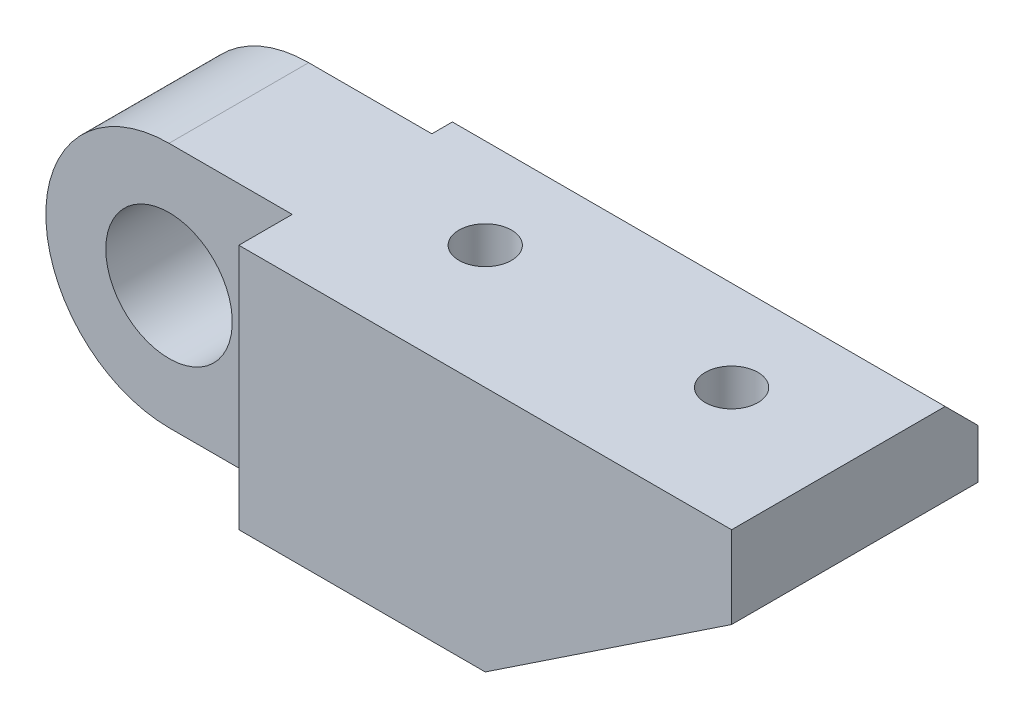
SolidWorks part; units mm, degrees
ref_plane "Front Plane" through (0, 0, 0) normal (0, 0, 1) x (1, 0, 0)
ref_plane "Top Plane" through (0, 0, 0) normal (0, 1, 0) x (1, 0, 0)
ref_plane "Right Plane" through (0, 0, 0) normal (1, 0, 0) x (0, 0, -1)
sketch "Sketch1" plane through (0, 0, 0) normal (0, 0, 1) x (1, 0, 0)
  line L0 (0, 0) -> (-15, 0)
  line L1 (0, 0) -> (60, 0)
  line L2 (0, 0) -> (0, -30)
  line L3 (0, -30) -> (60, -30)
  line L4 (60, 0) -> (60, -30)
  line L5 (-30, -15) -> (-30, 3.2539)
  line L6 (0, -30) -> (-15, -30)
  line L7 (0, 0) -> (0, -30)
  line L8 (-15, -30) -> (0, -30)
  line L9 (-15, 0) -> (0, 0)
  arc A0 (-15, -30) -> (-15, 0) centre (-15, -15) cw
  dimension "D1" = 60
  dimension "D2" = 30
  dimension "D3" = 30
extrude "Boss-Extrude2" add sketch "Sketch1" along normal blind 30 contours L2 L1 L4 L3
sketch "Sketch2" plane through (0, 0, 30) normal (0, 0, 1) x (1, 0, 0)
  line L0 (0, -30) -> (-15, -30) construction
  line L1 (0, 0) -> (-15, 0) construction
  line L2 (0, -30) -> (-15, -30)
  line L3 (0, 0) -> (-15, 0)
  arc A0 (-15, 0) -> (-15, -30) centre (-15, -15) ccw construction
  arc A1 (-15, 0) -> (-15, -30) centre (-15, -15) ccw
sketch "Sketch3" plane through (0, 0, 30) normal (0, 0, 1) x (1, 0, 0)
  line L0 (0, 0) -> (-15, 0)
  line L1 (0, -30) -> (-15, -30)
  line L2 (0, 0) -> (0, -30)
  arc A0 (-15, -30) -> (-15, 0) centre (-15, -15) cw
extrude "Boss-Extrude3" add sketch "Sketch3" against normal blind 30
sketch "Sketch4" plane through (0, 0, 30) normal (0, 0, 1) x (1, 0, 0)
  line L6 (-15, -30) -> (60, -30)
  line L7 (60, -30) -> (60, 0)
  line L8 (60, 0) -> (-15, 0)
  line L9 (-15, -30) -> (60, -30)
  line L10 (60, -30) -> (60, 0)
  line L11 (60, 0) -> (-15, 0)
  arc A2 (-15, 0) -> (-15, -30) centre (-15, -15) ccw
  arc A3 (-15, 0) -> (-15, -30) centre (-15, -15) ccw
  dimension "D1" = 0
sketch "Sketch5" plane through (0, 0, 30) normal (0, 0, 1) x (1, 0, 0)
  line L0 (0, 0) -> (0, -30)
  line L1 (0, -30) -> (-15, -30)
  line L2 (0, 0) -> (-15, 0)
  arc A0 (-15, -30) -> (-15, 0) centre (-15, -15) cw
extrude "Cut-Extrude1" cut sketch "Sketch5" against normal blind 6.5
sketch "Sketch6" plane through (0, 0, 0) normal (0, 0, -1) x (-1, 0, 0)
  line L0 (0, 0) -> (0, -30)
  line L1 (0, -30) -> (15, -30)
  line L2 (0, 0) -> (15, 0)
  arc A0 (15, 0) -> (15, -30) centre (15, -15) cw
extrude "Cut-Extrude2" cut sketch "Sketch6" against normal blind 6.5
sketch "Sketch7" plane through (0, 0, 6.5) normal (0, 0, -1) x (-1, 0, 0)
  circle A0 centre (15, -15) radius 7.7
  dimension "D1" = 15.4
extrude "Cut-Extrude3" cut sketch "Sketch7" against normal through all both and the other way through all
sketch "Sketch8" plane through (0, -30, 0) normal (0, -1, 0) x (1, 0, 0)
  line L0 (0, 30) -> (0, 0) construction
  line L1 (0, 0) -> (0, 15) construction
  line L2 (0, 15) -> (60, 15) construction
  line L3 (60, 30) -> (60, 0) construction
  line L4 (15, 30) -> (15, 0)
  line L5 (60, 30) -> (-15, 30) construction
  line L6 (0, 0) -> (60, 0) construction
  line L7 (45, 30) -> (45, 0)
  circle A0 centre (15, 15) radius 6
  circle A1 centre (45, 15) radius 6
  dimension "D3" = 12
  dimension "D4" = 12
  dimension "D1" = 15
  dimension "D2" = 15
extrude "Cut-Extrude6" cut sketch "Sketch8" against normal blind 6 contours A0
sketch "Sketch9" plane through (0, -30, 0) normal (0, -1, 0) x (1, 0, 0)
  circle A0 centre (45, 15) radius 6 construction
  circle A1 centre (45, 15) radius 6
extrude "Cut-Extrude7" cut sketch "Sketch9" against normal blind 16
sketch "Sketch10" plane through (0, -24, 0) normal (0, -1, 0) x (1, 0, 0)
  circle A0 centre (15, 15) radius 3.2
  circle A1 centre (45, 15) radius 3.2
  dimension "D1" = 6.4
  dimension "D2" = 6.4
extrude "Cut-Extrude8" cut sketch "Sketch10" against normal through all
chamfer "Chamfer2" distance 30 distance2 20 1 edges at (60, -30, 15) first distance on face at (45, -30, 9)
chamfer "Chamfer3" distance 4 angle 45 1 edges at (30, 0, 0)
